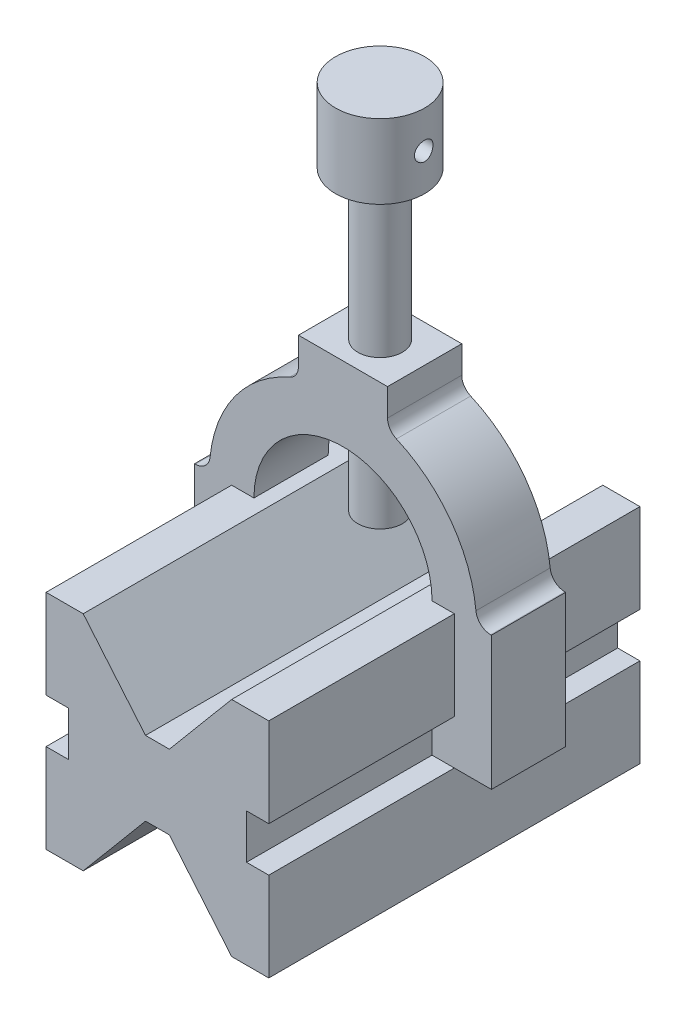
SolidWorks part; units mm, degrees
material "1060 Alloy"
ref_plane "Front Plane" through (0, 0, 0) normal (0, 0, 1) x (1, 0, 0)
ref_plane "Top Plane" through (0, 0, 0) normal (0, 1, 0) x (1, 0, 0)
ref_plane "Right Plane" through (0, 0, 0) normal (1, 0, 0) x (0, 0, -1)
sketch "Sketch2" plane through (0, 0, 0) normal (0, 0, 1) x (1, 0, 0)
  line L1 (-30, 30) -> (30, 30)
  line L2 (-30, 30) -> (-30, -30)
  line L3 (-30, -30) -> (30, -30)
  line L4 (30, 30) -> (30, -30)
  line L5 (-30, 30) -> (30, -30) construction
  line L6 (-30, -30) -> (30, 30) construction
  point P0 (0, 0)
  dimension "D1" = 60
extrude "Boss-Extrude1" add sketch "Sketch2" along normal blind 60 and the other way blind 40
sketch "Sketch3" plane through (0, 0, 60) normal (0, 0, 1) x (1, 0, 0)
  line L0 (0, 0) -> (30, 0) construction
  line L2 (0, 0) -> (-30, 0) construction
  line L3 (-30, 30) -> (-30, -30) construction
  line L4 (30, -30) -> (30, 30) construction
  line L5 (24, 6) -> (40, 6)
  line L6 (24, 6) -> (24, -6)
  line L7 (24, -6) -> (40, -6)
  line L8 (40, 6) -> (40, -6)
  line L9 (24, 6) -> (40, -6) construction
  line L10 (24, -6) -> (40, 6) construction
  line L11 (-24, 6) -> (-40, 6)
  line L12 (-24, 6) -> (-24, -6)
  line L13 (-24, -6) -> (-40, -6)
  line L14 (-40, 6) -> (-40, -6)
  line L15 (-24, 6) -> (-40, -6) construction
  line L16 (-24, -6) -> (-40, 6) construction
  point P3 (0, 0)
  point P17 (32, 0)
  point P18 (-32, 0)
  dimension "D1" = 16
  dimension "D2" = 6
  dimension "D3" = 12
  dimension "D4" = 6
  dimension "D5" = 12
  dimension "D6" = 16
extrude "Cut-Extrude1" cut sketch "Sketch3" against normal through all both and the other way through all
sketch "Sketch4" plane through (0, 0, 0) normal (0, 0, 1) x (1, 0, 0)
  line L0 (0, -30) -> (0, -10) construction
  line L1 (-30, -30) -> (30, -30) construction
  line L2 (0, -10) -> (-30, -10) construction
  line L3 (-30, -6) -> (-30, -30) construction
  line L4 (-30, -10) -> (30, -10) construction
  line L5 (30, -30) -> (30, -6) construction
  line L6 (-20, -30) -> (-3.218, -10)
  line L7 (-3.218, -10) -> (3.218, -10)
  line L8 (3.218, -10) -> (20, -30)
  line L9 (20, -30) -> (20, -54.7332)
  line L10 (20, -54.7332) -> (-20, -54.7332)
  line L11 (-20, -54.7332) -> (-20, -30)
  line L14 (30, 30) -> (-30, 30) construction
  line L15 (-20, 30) -> (-3.218, 10)
  line L16 (-3.218, 10) -> (3.218, 10)
  line L17 (3.218, 10) -> (20, 30)
  line L18 (20, 30) -> (20, 60.5471)
  line L19 (20, 60.5471) -> (-20, 60.5471)
  line L20 (-20, 60.5471) -> (-20, 30)
  line L21 (-30, 10) -> (-3.218, 10) construction
  line L22 (-30, 30) -> (-30, 6) construction
  line L23 (3.218, 10) -> (30, 10) construction
  line L24 (30, 6) -> (30, 30) construction
  point P13 (0, -10)
  point P18 (0, 10)
  dimension "D1" = 20
  dimension "D2" = 40
  dimension "D3" = 50
  dimension "D4" = 50
  dimension "D5" = 20
  dimension "D6" = 50
  dimension "D7" = 50
  dimension "D8" = 40
extrude "Cut-Extrude2" cut sketch "Sketch4" against normal through all both and the other way through all
sketch "Sketch5" plane through (0, 0, 0) normal (0, 0, 1) x (1, 0, 0)
  line L1 (24, -6) -> (40, -6)
  line L2 (24, -6) -> (24, 6)
  line L3 (24, 6) -> (40, 6)
  line L4 (40, -6) -> (40, 6)
  line L5 (-24, -6) -> (-40, -6)
  line L6 (-24, -6) -> (-24, 6)
  line L7 (-24, 6) -> (-40, 6)
  line L8 (-40, -6) -> (-40, 6)
  point P10 (-32.1474, 12.1673)
  dimension "D1" = 12
  dimension "D2" = 16
  dimension "D3" = 12
  dimension "D4" = 16
extrude "Boss-Extrude2" add sketch "Sketch5" along normal mid plane 20 separate body
sketch "Sketch7" plane through (0, 0, 0) normal (0, 0, 1) x (1, 0, 0)
  line L0 (40, -6) -> (40, 6) construction
  line L1 (-30, 6) -> (-40, 6)
  line L2 (-30, 6) -> (-30, 30)
  line L3 (-30, 30) -> (-40, 30)
  line L4 (-40, 6) -> (-40, 30)
  line L5 (30, 6) -> (40, 6)
  line L6 (30, 6) -> (30, 30)
  line L7 (30, 30) -> (40, 30)
  line L8 (40, 6) -> (40, 30)
  line L9 (-40, 6) -> (-40, -6) construction
  line L10 (-20, 30) -> (-30, 30) construction
  line L11 (30, 30) -> (20, 30) construction
extrude "Boss-Extrude3" add sketch "Sketch7" along normal mid plane 20 separate body
sketch "Sketch8" plane through (0, 0, 0) normal (0, 0, 1) x (1, 0, 0)
  line L0 (0, 0) -> (0, 36.5162) construction
  line L1 (-20, 30) -> (0, 30) construction
  line L2 (0, 30) -> (20, 30) construction
  line L5 (-20, 30) -> (-30, 30) construction
  line L6 (30, 30) -> (20, 30) construction
  line L7 (24, 30) -> (36, 30)
  line L8 (-24, 30) -> (-36, 30)
  arc A0 (-24, 30) -> (24, 30) centre (0, 30) cw
  arc A1 (-36, 30) -> (36, 30) centre (0, 30) cw
  dimension "D1" = 48
  dimension "D2" = 72
extrude "Boss-Extrude4" add sketch "Sketch8" along normal mid plane 20 separate body
combine bodies "Combine1" operation type add bodies to combine 108 107 106 105 104
sketch "Sketch10" plane through (0, 0, 0) normal (0, 0, 1) x (1, 0, 0)
  line L0 (0, 0) -> (0, 54) construction
  line L1 (0, 54) -> (0, 66) construction
  line L2 (0, 66) -> (0, 79.3054) construction
  line L4 (-12, 74) -> (12, 74)
  line L5 (-12, 74) -> (-12, 58)
  line L6 (-12, 58) -> (12, 58)
  line L7 (12, 74) -> (12, 58)
  line L8 (-12, 74) -> (12, 58) construction
  line L9 (-12, 58) -> (12, 74) construction
  line L10 (24, -6) -> (40, -6) construction
  arc A0 (24, 30) -> (-24, 30) centre (0, 30) ccw construction
  arc A1 (36, 30) -> (-36, 30) centre (0, 30) ccw construction
  dimension "D1" = 24
  dimension "D2" = 80
extrude "Boss-Extrude5" add sketch "Sketch10" along normal mid plane 20
fillet "Fillet1" radius 4 4 edges at (36, 30, 0) (-36, 30, 0) (-12, 63.9411, 0) (12, 63.9411, 0)
sketch "Sketch11" plane through (0, 0, 0) normal (0, 1, 0) x (1, 0, 0)
  circle A0 centre (0, 0) radius 6
  dimension "D1" = 12
extrude "Boss-Extrude6" add sketch "Sketch11" along normal blind 40 and the other way blind 40 from surface separate body starting at face at (0, 74, 0)
sketch "Sketch12" plane through (0, 0, 0) normal (0, 1, 0) x (1, 0, 0)
  circle A0 centre (0, 0) radius 12
  dimension "D1" = 24
extrude "Boss-Extrude7" add sketch "Sketch12" along normal blind 20 from surface separate body starting at face at (0, 114, -6)
combine bodies "Combine2" operation type add bodies to combine 112 111
sketch "Sketch13" plane through (0, 0, 0) normal (1, 0, 0) x (0, 0, -1)
  line L0 (-12, 124) -> (12, 124) construction
  line L1 (-12, 134) -> (-12, 114) construction
  line L2 (12, 114) -> (12, 134) construction
  circle A0 centre (0, 124) radius 2.5
  dimension "D1" = 5
extrude "Cut-Extrude4" cut sketch "Sketch13" against normal through all both and the other way through all
